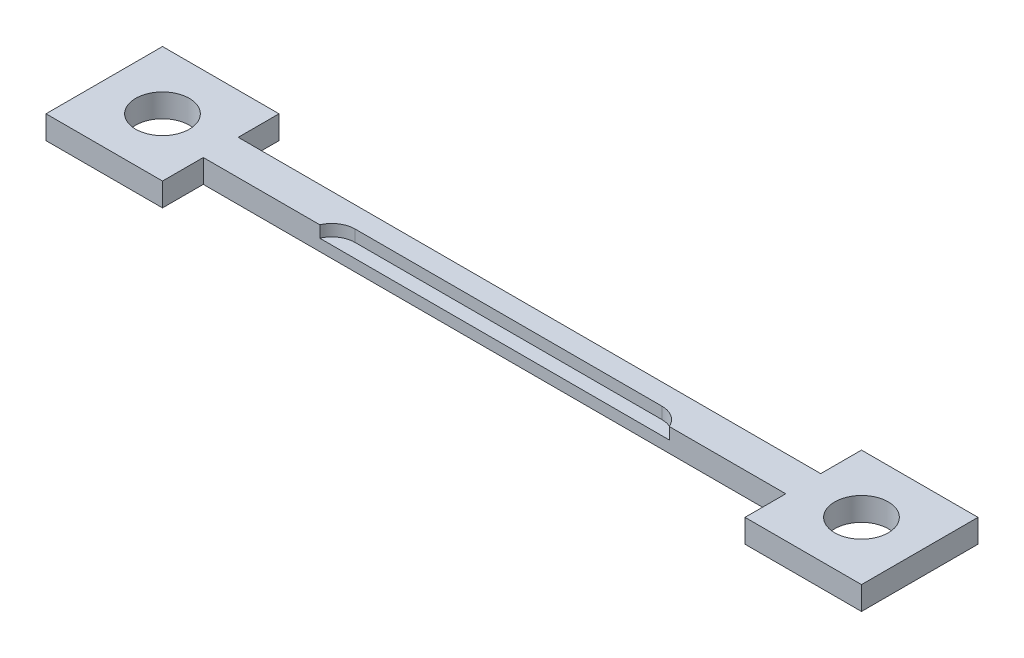
SolidWorks part; units mm, degrees
material "Commercially Pure CP-Ti UNS R50400 (SS)"
ref_plane "Front Plane" through (0, 0, 0) normal (0, 0, 1) x (1, 0, 0)
ref_plane "Top Plane" through (0, 0, 0) normal (0, 1, 0) x (1, 0, 0)
ref_plane "Right Plane" through (0, 0, 0) normal (1, 0, 0) x (0, 0, -1)
sketch "Sketch1" plane through (0, 0, 0) normal (0, 1, 0) x (1, 0, 0)
  line L0 (-41.424, -10.2833) -> (-41.424, -12.5058)
  line L1 (-47.774, -12.5058) -> (-41.424, -12.5058)
  line L2 (-47.774, -12.5058) -> (-47.774, -6.1558)
  line L3 (-47.774, -6.1558) -> (-41.424, -6.1558)
  line L4 (-3.324, -12.5058) -> (-3.324, -6.1558)
  line L7 (-41.424, -10.2833) -> (-9.674, -10.2833)
  line L9 (-41.424, -8.3783) -> (-9.674, -8.3783)
  line L13 (-41.424, -8.3783) -> (-41.424, -6.1558)
  line L14 (-9.674, -8.3783) -> (-9.674, -6.1558)
  line L15 (-9.674, -10.2833) -> (-9.674, -12.5058)
  line L16 (-9.674, -6.1558) -> (-3.324, -6.1558)
  line L17 (-9.674, -12.5058) -> (-3.324, -12.5058)
  point P0 (0, 0)
  point P6 (0, 0)
  dimension "D1" = 44.45
  dimension "D2" = 6.35
  dimension "D3" = 6.35
  dimension "D4" = 1.905
extrude "Boss-Extrude1" add sketch "Sketch1" along normal mid plane 1.27
hole_wizard "#97 (0.0059) Diameter Hole1" positions "Sketch4" profile "Sketch3" hole size "#97" standard "Ansi Inch" end condition through all
sketch "Sketch4" plane through (0, 0.635, 0) normal (0, 1, 0) x (-1, 0, 0)
  line L0 (47.774, 12.5058) -> (41.424, 6.1558) construction
  point P0 (44.599, 9.3308)
sketch "Sketch3" plane through (-44.599, 0.635, 9.3308) normal (1, 0, 0) x (0, 0, 1)
  line L0 (0, 0) -> (0, 1.27)
  line L1 (0, 1.27) -> (1.4605, 1.27)
  line L2 (1.4605, 1.27) -> (1.4605, 0)
  line L5 (1.4605, 0) -> (0, 0)
  line L11 (0, -6.35) -> (0, 107.95) construction
  dimension "Thru Hole Dia." = 2.921
  dimension "Thru Hole Depth" = 1.27
ref_plane "Plane1" through (-25.549, 0, 0) normal (1, 0, 0) x (0, 0, -1)
mirror "Mirror1" about plane through (-25.549, 0, 0) normal (1, 0, 0) of "#97 (0.0059) Diameter Hole1"
sketch "Sketch5" plane through (0, 0.635, 0) normal (0, 1, 0) x (1, 0, 0)
  line L2 (-41.424, -10.2833) -> (-9.674, -10.2833) construction
  line L3 (-35.074, -9.5213) -> (-16.024, -9.5213)
  line L4 (-35.074, -9.5213) -> (-35.074, -10.2833)
  line L5 (-35.074, -10.2833) -> (-16.024, -10.2833)
  line L6 (-16.024, -9.5213) -> (-16.024, -10.2833)
extrude "Cut-Extrude1" cut sketch "Sketch5" against normal blind 0.635
fillet "Fillet4" radius 1.27 1 edges at (-35.074, 0.3175, 9.5213)
fillet "Fillet5" radius 1.27 1 edges at (-16.024, 0.3175, 9.5213)
